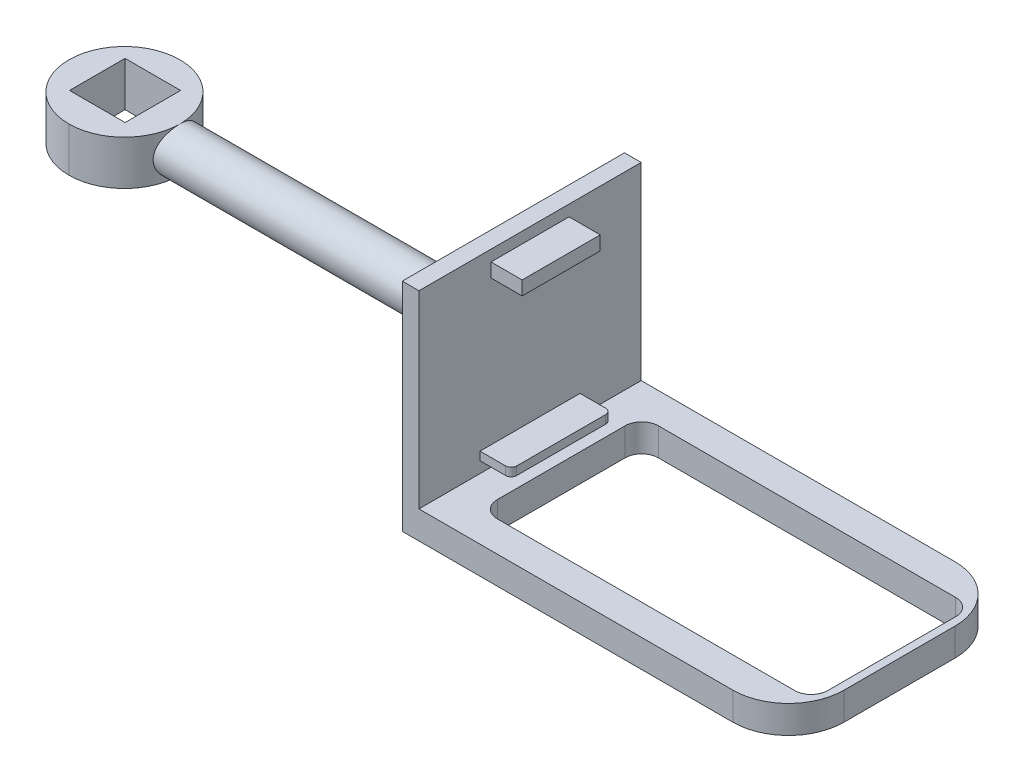
SolidWorks part; units mm, degrees
ref_plane "Front Plane" through (0, 0, 0) normal (0, 0, 1) x (1, 0, 0)
ref_plane "Top Plane" through (0, 0, 0) normal (0, 1, 0) x (1, 0, 0)
ref_plane "Right Plane" through (0, 0, 0) normal (1, 0, 0) x (0, 0, -1)
sketch "Sketch2" plane through (0, 0, 0) normal (0, 1, 0) x (1, 0, 0)
  line L0 (-27.65, 11.5) -> (-27.65, -11.5)
  line L7 (-33.25, -20) -> (33.25, -20)
  line L8 (-33.25, -20) -> (-33.25, 20)
  line L9 (-33.25, 20) -> (33.25, 20)
  line L10 (33.25, -20) -> (33.25, 20)
  line L11 (-24.65, 14.5) -> (28.85, 14.5)
  line L12 (31.85, 11.5) -> (31.85, -11.5)
  line L13 (28.85, -14.5) -> (-24.65, -14.5)
  arc A4 (31.85, -11.5) -> (28.85, -14.5) centre (28.85, -11.5) cw
  arc A5 (28.85, 14.5) -> (31.85, 11.5) centre (28.85, 11.5) cw
  arc A6 (-27.65, 11.5) -> (-24.65, 14.5) centre (-24.65, 11.5) cw
  arc A7 (-27.65, -11.5) -> (-24.65, -14.5) centre (-24.65, -11.5) ccw
  point P0 (0, 0)
  point P7 (0, 0)
  dimension "D1" = 3
extrude "Boss-Extrude1" add sketch "Sketch2" along normal blind 5
sketch "Sketch5" plane through (-33.25, 0, 0) normal (-1, 0, 0) x (0, 0, 1)
  line L1 (20, 0) -> (-20, 0)
  line L2 (20, 0) -> (20, 39)
  line L3 (20, 39) -> (-20, 39)
  line L4 (-20, 0) -> (-20, 39)
  dimension "D1" = 39
extrude "Boss-Extrude3" add sketch "Sketch5" along normal blind 3
sketch "Sketch11" plane through (-33.25, 0, 0) normal (1, 0, 0) x (0, 0, -1)
  line L6 (0, 37) -> (-7.025, 37)
  line L7 (0, 37) -> (7.025, 37)
  line L11 (-7.025, 37) -> (-7.025, 34.5)
  line L12 (-7.025, 34.5) -> (7.025, 34.5)
  line L13 (7.025, 34.5) -> (7.025, 37)
  line L14 (0, 7) -> (-9, 7)
  line L15 (0, 7) -> (9, 7)
  line L16 (9, 7) -> (9, 8.5)
  line L17 (9, 8.5) -> (-9, 8.5)
  line L18 (-9, 8.5) -> (-9, 7)
extrude "Boss-Extrude4" add sketch "Sketch11" along normal blind 5.6 contours L12 L13 L7 L6 L11 | L15 L16 L17 L18 L14
fillet "Fillet4" radius 1 2 edges at (-27.65, 7.75, 9) (-27.65, 7.75, -9)
sketch "Sketch12" plane through (-36.25, 0, 0) normal (-1, 0, 0) x (0, 0, 1)
  circle A0 centre (0, 19.5) radius 4
extrude "Boss-Extrude5" add sketch "Sketch12" along normal blind 60
sketch "Sketch13" plane through (-96.25, 0, 0) normal (-1, 0, 0) x (0, 0, 1)
  line L1 (-10, 15.5) -> (10, 15.5)
  line L2 (-10, 15.5) -> (-10, 23.5)
  line L3 (-10, 23.5) -> (10, 23.5)
  line L4 (10, 15.5) -> (10, 23.5)
  line L5 (-10, 15.5) -> (10, 23.5) construction
  line L6 (-10, 23.5) -> (10, 15.5) construction
  point P0 (0, 19.5)
extrude "Boss-Extrude6" add sketch "Sketch13" along normal blind 20
sketch "Sketch14" plane through (0, 23.5, 0) normal (0, 1, 0) x (1, 0, 0)
  line L1 (-111.4127, 5.2751) -> (-101.4127, 5.2751)
  line L2 (-111.4127, 5.2751) -> (-111.4127, -4.7249)
  line L3 (-111.4127, -4.7249) -> (-101.4127, -4.7249)
  line L4 (-101.4127, 5.2751) -> (-101.4127, -4.7249)
  line L5 (-111.4127, 5.2751) -> (-101.4127, -4.7249) construction
  line L6 (-111.4127, -4.7249) -> (-101.4127, 5.2751) construction
  point P0 (-106.4127, 0.2751)
  dimension "D1" = 10
  dimension "D2" = 10
extrude "Cut-Extrude1" cut sketch "Sketch14" against normal blind 20
fillet "Fillet5" radius 10 4 edges at (-116.25, 19.5, -10) (-96.25, 19.5, 10) (-96.25, 19.5, -10) (-116.25, 19.5, 10)
fillet "Fillet6" radius 10 2 edges at (33.25, 2.5, 20) (33.25, 2.5, -20)
